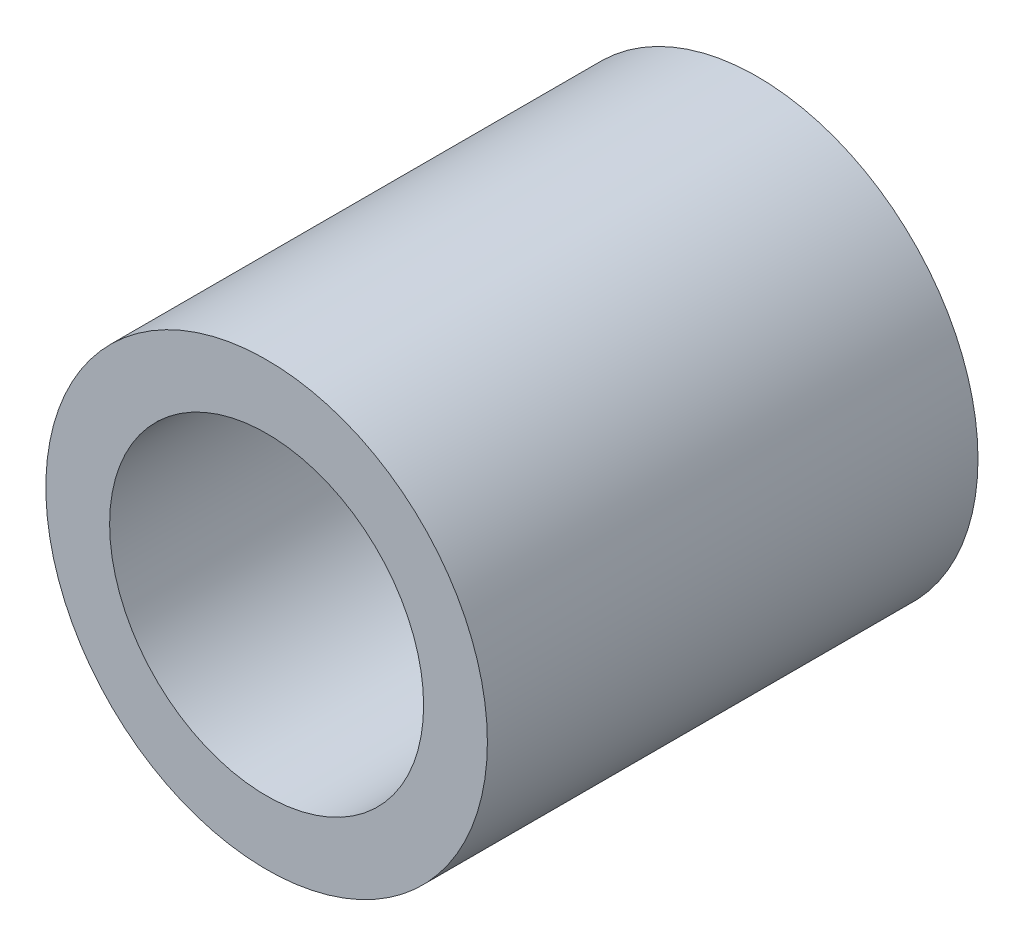
SolidWorks part; units mm, degrees
ref_plane "Front Plane" through (0, 0, 0) normal (0, 0, 1) x (1, 0, 0)
ref_plane "Top Plane" through (0, 0, 0) normal (0, 1, 0) x (1, 0, 0)
ref_plane "Right Plane" through (0, 0, 0) normal (1, 0, 0) x (0, 0, -1)
sketch "Sketch1" plane through (0, 0, 0) normal (0, 0, 1) x (1, 0, 0)
  circle A0 centre (0, 0) radius 2.25
  circle A1 centre (0, 0) radius 1.6
  dimension "OD" = 4.5
  dimension "ID" = 3.2
extrude "Extrude1" add sketch "Sketch1" along normal mid plane 5
sketch "Sketch2" plane through (0, 0, 0) normal (1, 0, 0) x (0, 0, -1)
  line L0 (-2.5, -1.6) -> (2.5, -1.6) construction
  line L3 (2.5, 1.6) -> (-2.5, 1.6) construction
  line L5 (-2.5, -1.6) -> (2.5, -1.6)
  line L6 (2.5, 1.6) -> (-2.5, 1.6)
sketch "Sketch4" plane through (0, 0, 2.5) normal (0, 0, 1) x (1, 0, 0)
  line L0 (0, 0) -> (-1.1314, 1.1314)
  line L1 (0, -1.1) -> (0, 1.1) construction
  circle A0 centre (0, 0) radius 1.6 construction
  dimension "D1" = 45
ref_plane "Plane1" through (0, 0, 0) normal (0, 0, 1) x (1, 0, 0)
